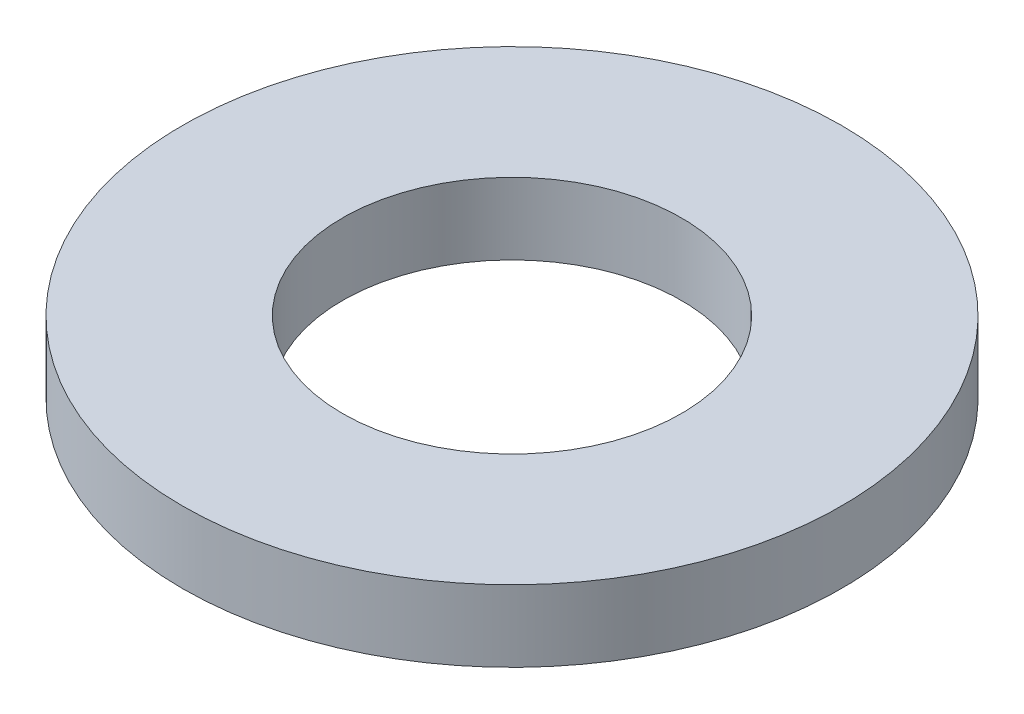
SolidWorks part; units mm, degrees
ref_plane "Front Plane" through (0, 0, 0) normal (0, 0, 1) x (1, 0, 0)
ref_plane "Top Plane" through (0, 0, 0) normal (0, 1, 0) x (1, 0, 0)
ref_plane "Right Plane" through (0, 0, 0) normal (1, 0, 0) x (0, 0, -1)
sketch "Sketch1" plane through (0, 0, 0) normal (0, 1, 0) x (1, 0, 0)
  circle A0 centre (0, 0) radius 87.5
  dimension "FLANGE_OD" = 175
extrude "Boss-Extrude1" add sketch "Sketch1" along normal blind 19
sketch "Sketch2" plane through (0, 0, 0) normal (0, 1, 0) x (1, 0, 0)
  circle A0 centre (0, 0) radius 45
  dimension "BORE_D" = 90
extrude "Cut-Extrude1" cut sketch "Sketch2" along normal through all
sketch "Sketch3" plane through (0, 19, 0) normal (0, 1, 0) x (1, 0, 0)
  circle A0 centre (0, 0) radius 29.7178 construction
  circle A1 centre (-29.7178, 0) radius 4.2187
  dimension "BOLT_D" = 8.4375
  dimension "BOLT_PCD" = 59.4355
extrude "Cut-Extrude2" cut sketch "Sketch3" against normal blind 17.8634 rebuild error yes
pattern_circular "CirPattern1" count 3 over 360 rebuild error yes
